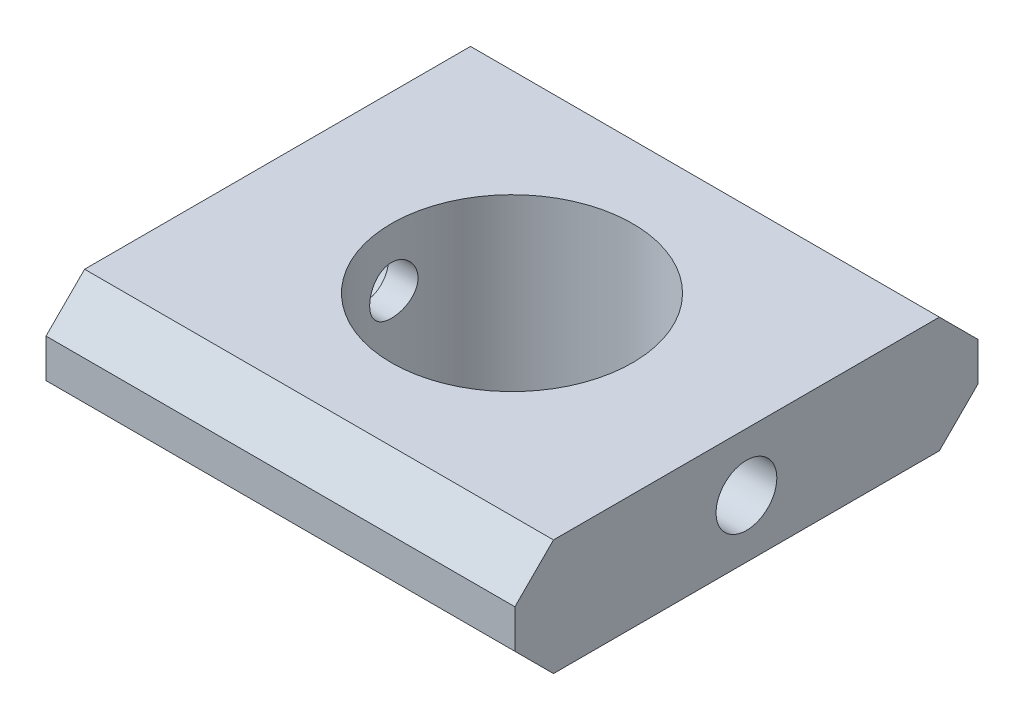
SolidWorks part; units mm, degrees
ref_plane "Front Plane" through (0, 0, 0) normal (0, 0, 1) x (1, 0, 0)
ref_plane "Top Plane" through (0, 0, 0) normal (0, 1, 0) x (1, 0, 0)
ref_plane "Right Plane" through (0, 0, 0) normal (1, 0, 0) x (0, 0, -1)
sketch "Sketch4" plane through (0, 0, 0) normal (0, 1, 0) x (1, 0, 0)
  circle A0 centre (0, 0) radius 10.16
  dimension "D1" = 20.32
extrude "Boss-Extrude1" add sketch "Sketch4" along normal blind 2.54 and the other way blind 2.54
sketch "Sketch5" plane through (0, 0, 0) normal (0, 1, 0) x (1, 0, 0)
  circle A0 centre (0, 0) radius 8.89
  circle A1 centre (0, 0) radius 10.16 construction
  circle A2 centre (0, 0) radius 10.16
  dimension "D1" = 1.27
extrude "Cut-Extrude1" cut sketch "Sketch5" against normal blind 1.27 and the other way blind 1.27 contours A2 A0 region at (-9.8726, 0, 0)
fillet "Fillet1" radius 1.27 2 edges at (0, -1.27, 8.89) (0, 1.27, 8.89)
sketch "Sketch6" plane through (0, 2.54, 0) normal (0, 1, 0) x (1, 0, 0)
  circle A0 centre (0, 0) radius 7.9375
  dimension "D1" = 15.875
extrude "Cut-Extrude2" cut sketch "Sketch6" against normal through all
sketch "Sketch7" plane through (0, 2.54, 0) normal (0, 1, 0) x (1, 0, 0)
  line L1 (-15.24, -15.24) -> (15.24, -15.24)
  line L2 (-15.24, -15.24) -> (-15.24, 15.24)
  line L3 (-15.24, 15.24) -> (15.24, 15.24)
  line L4 (15.24, -15.24) -> (15.24, 15.24)
  line L5 (-15.24, -15.24) -> (15.24, 15.24) construction
  line L6 (-15.24, 15.24) -> (15.24, -15.24) construction
  circle A0 centre (0, 0) radius 7.9375
  point P0 (0, 0)
  circle M7 centre (0, 0) radius 10.16
  dimension "D1" = 30.48
  dimension "D2" = 30.48
extrude "Boss-Extrude2" add sketch "Sketch7" against normal blind 1.27 contours L1 L4 L3 L2 M7 region at (-14.8089, 2.54, 0)
sketch "Sketch8" plane through (0, 2.54, 0) normal (0, 1, 0) x (1, 0, 0)
  line L1 (-15.24, -15.24) -> (15.24, -15.24)
  line L2 (-15.24, -15.24) -> (-15.24, 15.24)
  line L3 (-15.24, 15.24) -> (15.24, 15.24)
  line L4 (15.24, -15.24) -> (15.24, 15.24)
  line L5 (-15.24, -15.24) -> (15.24, 15.24) construction
  line L6 (-15.24, 15.24) -> (15.24, -15.24) construction
  circle A0 centre (0, 0) radius 7.9375
extrude "Boss-Extrude3" add sketch "Sketch8" along normal blind 1.27
sketch "Sketch9" plane through (0, 0, 15.24) normal (0, 0, 1) x (1, 0, 0)
  line L0 (-15.24, 3.81) -> (-15.24, 1.27)
  line L4 (-15.24, 1.27) -> (-12.7, 1.27)
  line L5 (-15.24, 1.27) -> (15.24, 1.27) construction
  line L6 (-12.7, 1.27) -> (-15.24, 3.81)
  dimension "D1" = 45
extrude "Cut-Extrude3" cut sketch "Sketch9" against normal through all
mirror "Mirror2" about plane through (0, 0, 0) normal (1, 0, 0) of "Cut-Extrude3"
sketch "Sketch11" plane through (0, 0, 0) normal (1, 0, 0) x (0, 0, -1)
  line L0 (-15.24, 3.81) -> (-12.7, 1.27)
  line L1 (15.24, 1.27) -> (-15.24, 1.27) construction
  line L2 (-12.7, 1.27) -> (-15.24, 1.27)
  line L3 (-15.24, 1.27) -> (-15.24, 3.81)
  dimension "D1" = 45
extrude "Cut-Extrude4" cut sketch "Sketch11" against normal through all and the other way through all
mirror "Mirror3" about plane through (0, 0, 0) normal (0, 0, 1) of "Cut-Extrude4"
sketch "Sketch12" plane through (0, 0, 0) normal (1, 0, 0) x (0, 0, -1)
  line L0 (-15.24, 3.81) -> (-5.4983, -5.9317)
  line L1 (-5.4983, -5.9317) -> (-15.24, -5.9317)
  line L2 (-15.24, -5.9317) -> (-15.24, 3.81)
extrude "Cut-Extrude5" cut sketch "Sketch12" against normal through all and the other way through all
mirror "Mirror4" about plane through (0, 0, 0) normal (0, 0, 1) of "Cut-Extrude5"
sketch "Sketch13" plane through (0, 0, 0) normal (0, 0, 1) x (1, 0, 0)
  line L0 (-15.24, 3.81) -> (-1.4289, -10.0011)
  line L1 (-1.4289, -10.0011) -> (-15.24, -10.0011)
  line L2 (-15.24, -10.0011) -> (-15.24, 3.81)
extrude "Cut-Extrude6" cut sketch "Sketch13" against normal through all and the other way through all
mirror "Mirror5" about plane through (0, 0, 0) normal (1, 0, 0) of "Cut-Extrude6"
sketch "Sketch14" plane through (0, 0, 0) normal (0, 0, 1) x (1, 0, 0)
  line L1 (-19.05, -1.1554) -> (-11.43, -1.1554)
  line L2 (-19.05, -1.1554) -> (-19.05, 8.7754)
  line L3 (-19.05, 8.7754) -> (-11.43, 8.7754)
  line L4 (-11.43, -1.1554) -> (-11.43, 8.7754)
  line L5 (-19.05, -1.1554) -> (-11.43, 8.7754) construction
  line L6 (-19.05, 8.7754) -> (-11.43, -1.1554) construction
  point P0 (-15.24, 3.81)
  dimension "D1" = 3.81
extrude "Cut-Extrude7" cut sketch "Sketch14" against normal through all and the other way through all
mirror "Mirror6" about plane through (0, 0, 0) normal (1, 0, 0) of "Cut-Extrude7"
sketch "Sketch15" plane through (0, 3.81, 0) normal (0, 1, 0) x (1, 0, 0)
  line L1 (-11.43, -15.24) -> (11.43, -15.24)
  line L2 (-11.43, -15.24) -> (-11.43, 15.24)
  line L3 (-11.43, 15.24) -> (11.43, 15.24)
  line L4 (11.43, -15.24) -> (11.43, 15.24)
  line L5 (-11.43, -15.24) -> (11.43, 15.24) construction
  line L6 (-11.43, 15.24) -> (11.43, -15.24) construction
  circle A0 centre (0, 0) radius 7.9375
  circle M1 centre (0, 0) radius 7.9375
  line M2 (11.43, -15.24) -> (11.43, 15.24)
  line M3 (11.43, 15.24) -> (-11.43, 15.24)
  line M4 (-11.43, 15.24) -> (-11.43, -15.24)
  line M5 (-11.43, -15.24) -> (11.43, -15.24)
extrude "Boss-Extrude4" add sketch "Sketch15" along normal blind 5.08 contours M5 M2 M3 M4 M1 region at (-11.049, 3.81, 0)
sketch "Sketch16" plane through (0, 0, 0) normal (1, 0, 0) x (0, 0, -1)
  line L0 (-15.24, 3.81) -> (0, -11.43) construction
  line L1 (0, -11.43) -> (15.24, 3.81) construction
  line L2 (-15.24, 3.81) -> (-12.7, 1.27) construction
  line L3 (15.24, 3.81) -> (12.7, 1.27) construction
  circle A0 centre (0, -11.43) radius 23.8125
  circle A1 centre (0, -11.43) radius 32.7675
  circle A2 centre (0, 5.08) radius 1.59
  dimension "D1" = 47.625
  dimension "D3" = 3.18
  dimension "D2" = 16.51
extrude "Cut-Extrude8" cut sketch "Sketch16" against normal through all and the other way through all contours A2
sketch "Sketch18" plane through (11.43, 0, 0) normal (1, 0, 0) x (0, 0, -1)
  line L0 (-15.24, 3.81) -> (-12.7, 1.27)
  line L1 (-12.7, 1.27) -> (12.7, 1.27)
  line L2 (12.7, 1.27) -> (15.24, 3.81)
  line L3 (15.24, 3.81) -> (15.24, 8.89)
  line L4 (15.24, 8.89) -> (-15.24, 8.89)
  line L5 (-15.24, 8.89) -> (-15.24, 3.81)
  circle A0 centre (0, 5.08) radius 2
extrude "Boss-Extrude5" add sketch "Sketch18" along normal blind 4
mirror "Mirror7" about plane through (0, 0, 0) normal (1, 0, 0) of "Boss-Extrude5"
sketch "Sketch19" plane through (15.43, 0, 0) normal (1, 0, 0) x (0, 0, -1)
  circle A0 centre (0, 5.08) radius 2
  dimension "D1" = 4
extrude "Cut-Extrude9" cut sketch "Sketch19" against normal blind 5.7
mirror "Mirror8" about plane through (0, 0, 0) normal (1, 0, 0) of "Cut-Extrude9"
chamfer "Chamfer1" distance 2.54 angle 45 2 edges at (0, 8.89, -15.24) (0, 8.89, 15.24)
